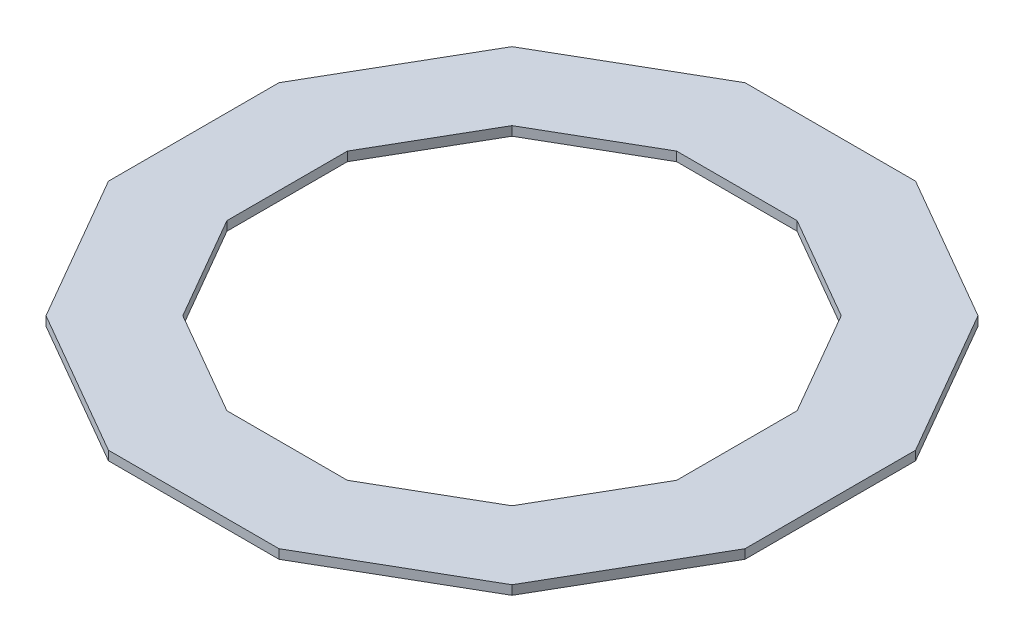
SolidWorks part; units mm, degrees
material "ABS PC"
ref_plane "Front Plane" through (0, 0, 0) normal (0, 0, 1) x (1, 0, 0)
ref_plane "Top Plane" through (0, 0, 0) normal (0, 1, 0) x (1, 0, 0)
ref_plane "Right Plane" through (0, 0, 0) normal (1, 0, 0) x (0, 0, -1)
sketch "Sketch1" plane through (0, 0, 0) normal (0, 1, 0) x (1, 0, 0)
  line L0 (26.296, 98.1381) -> (-26.296, 98.1381)
  line L1 (-26.296, 98.1381) -> (-71.842, 71.842)
  line L2 (-71.842, 71.842) -> (-98.1381, 26.296)
  line L3 (-98.1381, 26.296) -> (-98.1381, -26.296)
  line L4 (-98.1381, -26.296) -> (-71.842, -71.842)
  line L5 (-71.842, -71.842) -> (-26.296, -98.1381)
  line L6 (-26.296, -98.1381) -> (26.296, -98.1381)
  line L7 (26.296, -98.1381) -> (71.842, -71.842)
  line L8 (71.842, -71.842) -> (98.1381, -26.296)
  line L9 (98.1381, -26.296) -> (98.1381, 26.296)
  line L10 (98.1381, 26.296) -> (71.842, 71.842)
  line L11 (71.842, 71.842) -> (26.296, 98.1381)
  circle A0 centre (0, 0) radius 101.6
  dimension "D1" = 203.2
extrude "Boss-Extrude1" add sketch "Sketch1" against normal blind 2.921 contours L10 L11 L0 L1 L2 L3 L4 L5 L6 L7 L8 L9 region at (0, 0, 0)
sketch "Sketch3" plane through (0, 0, 0) normal (0, 1, 0) x (1, 0, 0)
  line L12 (-52.2651, 52.2651) -> (-19.1304, 71.3954)
  line L13 (-19.1304, 71.3954) -> (19.1304, 71.3954)
  line L14 (19.1304, 71.3954) -> (52.2651, 52.2651)
  line L15 (52.2651, 52.2651) -> (71.3954, 19.1304)
  line L16 (71.3954, 19.1304) -> (71.3954, -19.1304)
  line L17 (71.3954, -19.1304) -> (52.2651, -52.2651)
  line L18 (52.2651, -52.2651) -> (19.1304, -71.3954)
  line L19 (19.1304, -71.3954) -> (-19.1304, -71.3954)
  line L20 (-19.1304, -71.3954) -> (-52.2651, -52.2651)
  line L21 (-52.2651, -52.2651) -> (-71.3954, -19.1304)
  line L22 (-71.3954, -19.1304) -> (-71.3954, 19.1304)
  line L23 (-71.3954, 19.1304) -> (-52.2651, 52.2651)
  line L24 (-71.842, 71.842) -> (-98.1381, 26.296) construction
  line L25 (-26.296, 98.1381) -> (-71.842, 71.842) construction
  line L26 (26.296, 98.1381) -> (-26.296, 98.1381) construction
  line L27 (71.842, 71.842) -> (26.296, 98.1381) construction
  line L28 (98.1381, 26.296) -> (71.842, 71.842) construction
  line L29 (98.1381, -26.296) -> (98.1381, 26.296) construction
  line L30 (71.842, -71.842) -> (98.1381, -26.296) construction
  line L31 (26.296, -98.1381) -> (71.842, -71.842) construction
  line L32 (-26.296, -98.1381) -> (26.296, -98.1381) construction
  line L33 (-71.842, -71.842) -> (-26.296, -98.1381) construction
  line L34 (-98.1381, -26.296) -> (-71.842, -71.842) construction
  line L35 (-98.1381, 26.296) -> (-98.1381, -26.296) construction
  line L36 (-26.296, 98.1381) -> (26.296, -98.1381) construction
  line L37 (26.296, 98.1381) -> (-26.296, -98.1381) construction
  circle A0 centre (0, 0) radius 73.914
  dimension "D1" = 147.828
extrude "Cut-Extrude1" cut sketch "Sketch3" against normal through all contours L23 L22 L21 L20 L19 L18 L17 L16 L15 L14 L13 L12 region at (0, 0, 0)
sketch "Sketch4" plane through (0, 0, 0) normal (0, 1, 0) x (1, 0, 0)
  line L24 (101.0591, 27.0787) -> (73.9804, 73.9804)
  line L25 (73.9804, 73.9804) -> (27.0787, 101.0591)
  line L26 (27.0787, 101.0591) -> (-27.0787, 101.0591)
  line L27 (-27.0787, 101.0591) -> (-73.9804, 73.9804)
  line L28 (-73.9804, 73.9804) -> (-101.0591, 27.0787)
  line L29 (-101.0591, 27.0787) -> (-101.0591, -27.0787)
  line L30 (-101.0591, -27.0787) -> (-73.9804, -73.9804)
  line L31 (-73.9804, -73.9804) -> (-27.0787, -101.0591)
  line L32 (-27.0787, -101.0591) -> (27.0787, -101.0591)
  line L33 (27.0787, -101.0591) -> (73.9804, -73.9804)
  line L34 (73.9804, -73.9804) -> (101.0591, -27.0787)
  line L35 (101.0591, -27.0787) -> (101.0591, 27.0787)
  line L36 (101.0591, 27.0787) -> (73.9804, 73.9804)
  line L37 (73.9804, 73.9804) -> (27.0787, 101.0591)
  line L38 (27.0787, 101.0591) -> (-27.0787, 101.0591)
  line L39 (-27.0787, 101.0591) -> (-73.9804, 73.9804)
  line L40 (-73.9804, 73.9804) -> (-101.0591, 27.0787)
  line L41 (-101.0591, 27.0787) -> (-101.0591, -27.0787)
  line L42 (-101.0591, -27.0787) -> (-73.9804, -73.9804)
  line L43 (-73.9804, -73.9804) -> (-27.0787, -101.0591)
  line L44 (-27.0787, -101.0591) -> (27.0787, -101.0591)
  line L45 (27.0787, -101.0591) -> (73.9804, -73.9804)
  line L46 (73.9804, -73.9804) -> (101.0591, -27.0787)
  line L47 (101.0591, -27.0787) -> (101.0591, 27.0787)
  line L60 (98.1381, 26.296) -> (71.842, 71.842)
  line L61 (71.842, 71.842) -> (26.296, 98.1381)
  line L62 (26.296, 98.1381) -> (-26.296, 98.1381)
  line L63 (-26.296, 98.1381) -> (-71.842, 71.842)
  line L64 (-71.842, 71.842) -> (-98.1381, 26.296)
  line L65 (-98.1381, 26.296) -> (-98.1381, -26.296)
  line L66 (-98.1381, -26.296) -> (-71.842, -71.842)
  line L67 (-71.842, -71.842) -> (-26.296, -98.1381)
  line L68 (-26.296, -98.1381) -> (26.296, -98.1381)
  line L69 (26.296, -98.1381) -> (71.842, -71.842)
  line L70 (71.842, -71.842) -> (98.1381, -26.296)
  line L71 (98.1381, -26.296) -> (98.1381, 26.296)
  line L72 (98.1381, 26.296) -> (71.842, 71.842)
  line L73 (71.842, 71.842) -> (26.296, 98.1381)
  line L74 (26.296, 98.1381) -> (-26.296, 98.1381)
  line L75 (-26.296, 98.1381) -> (-71.842, 71.842)
  line L76 (-71.842, 71.842) -> (-98.1381, 26.296)
  line L77 (-98.1381, 26.296) -> (-98.1381, -26.296)
  line L78 (-98.1381, -26.296) -> (-71.842, -71.842)
  line L79 (-71.842, -71.842) -> (-26.296, -98.1381)
  line L80 (-26.296, -98.1381) -> (26.296, -98.1381)
  line L81 (26.296, -98.1381) -> (71.842, -71.842)
  line L82 (71.842, -71.842) -> (98.1381, -26.296)
  line L83 (98.1381, -26.296) -> (98.1381, 26.296)
  dimension "D1" = 2.921
  dimension "D2" = 0
extrude "Boss-Extrude2" add sketch "Sketch4" against normal up to surface (2.921 mm away) up to face at (0, -2.921, 0)
